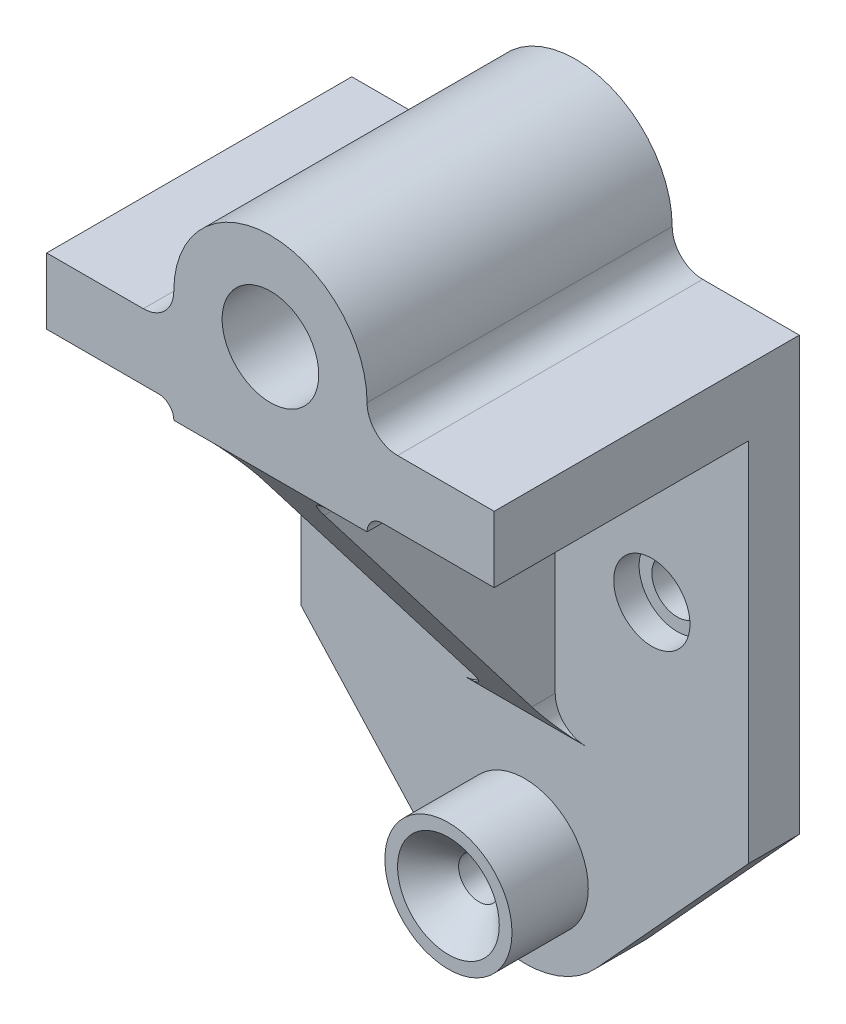
SolidWorks part; units mm, degrees
note: The reader was unsure of these and kept them because the rebuilt part matched: shared geometry of "Sketch5<11>", "Sketch2<10>", "Sketch5<9>".
ref_plane "Front Plane" through (0, 0, 0) normal (0, 0, 1) x (1, 0, 0)
ref_plane "Top Plane" through (0, 0, 0) normal (0, 1, 0) x (1, 0, 0)
ref_plane "Right Plane" through (0, 0, 0) normal (1, 0, 0) x (0, 0, -1)
sketch "Sketch2" plane through (0, 0, 0) normal (0, 0, 1) x (1, 0, 0)
  line L0 (44, 20) -> (14.0289, -12.8136)
  line L1 (44, 20) -> (44, 105)
  line L2 (44, 105) -> (25, 105)
  line L3 (0, 0) -> (0, 156.6134) construction
  line L4 (12, 89) -> (-12, 89)
  line L5 (44, 92) -> (22, 92)
  line L6 (-12, 24) -> (-9.5, 24)
  line L7 (19, 89) -> (12, 89)
  line L8 (6, 83) -> (6, 30)
  line L9 (12, 24) -> (9.5, 24)
  line L10 (9.5, 24) -> (-9.5, 24)
  line L11 (-6, 83) -> (-6, 30)
  line L12 (-19, 89) -> (-12, 89)
  line L13 (-44, 92) -> (-22, 92)
  line L14 (-44, 105) -> (-25, 105)
  line L15 (-44, 20) -> (-44, 105)
  line L16 (-44, 20) -> (-14.0289, -12.8136)
  arc A0 (-14.0289, -12.8136) -> (14.0289, -12.8136) centre (0, 0) ccw
  arc A1 (19, 111) -> (-19, 111) centre (0, 111) ccw
  arc A2 (25, 105) -> (19, 111) centre (25, 111) cw
  arc A3 (0, 101.5) -> (0, 120.5) centre (0, 111) ccw
  circle A4 centre (0, 0) radius 12.5
  circle A5 centre (0, 0) radius 4
  arc A6 (12, 24) -> (6, 30) centre (12, 30) cw
  arc A7 (12, 89) -> (6, 83) centre (12, 83) ccw
  arc A8 (22, 92) -> (19, 89) centre (22, 89) ccw
  circle A11 centre (0, 0) radius 10
  arc A14 (-22, 92) -> (-19, 89) centre (-22, 89) cw
  arc A15 (-12, 89) -> (-6, 83) centre (-12, 83) cw
  arc A16 (-12, 24) -> (-6, 30) centre (-12, 30) ccw
  arc A17 (0, 101.5) -> (0, 120.5) centre (0, 111) cw
  arc A18 (-25, 105) -> (-19, 111) centre (-25, 111) ccw
  point P30 (6, 24)
  point P40 (9.5, 111)
  point P52 (0, 24)
  point P53 (0, 89)
  dimension "D1" = 19
  dimension "D2" = 19
  dimension "D3" = 6
  dimension "D4" = 13
  dimension "D6" = 25
  dimension "D7" = 8
  dimension "D14" = 6
  dimension "D15" = 6
  dimension "D16" = 6
  dimension "D21" = 20
  dimension "D22" = 19
  dimension "D5" = 72
  dimension "D8" = 105
  dimension "D9" = 22
  dimension "D10" = 13
  dimension "D11" = 81
  dimension "D12" = 65
  dimension "D13" = 25
extrude "Boss-Extrude6" add sketch "Sketch2" along normal blind 60 contours A18 A1 A2 L2 L1 L0 A0 L16 L15 L14
sketch "Sketch5" plane through (0, 0, 60) normal (0, 0, 1) x (1, 0, 0)
  line L0 (44, 20) -> (44, 105) construction
  line L1 (-44, 20) -> (-44, 105) construction
  line L2 (12, 24) -> (9.5, 24) construction
  line L3 (-12, 24) -> (-9.5, 24) construction
  line L4 (9.5, 24) -> (-9.5, 24) construction
  line L5 (-44, 20) -> (-14.0289, -12.8136) construction
  line L6 (44, 20) -> (14.0289, -12.8136) construction
  line L7 (44, 92) -> (22, 92) construction
  line L8 (19, 89) -> (12, 89) construction
  line L9 (6, 83) -> (6, 30) construction
  line L10 (12, 89) -> (-12, 89) construction
  line L11 (-6, 83) -> (-6, 30) construction
  line L12 (-19, 89) -> (-12, 89) construction
  line L13 (-44, 92) -> (-22, 92) construction
  line L14 (44, 20) -> (44, 105)
  line L15 (-44, 20) -> (-44, 105)
  line L16 (12, 24) -> (9.5, 24)
  line L17 (-12, 24) -> (-9.5, 24)
  line L18 (9.5, 24) -> (-9.5, 24)
  line L19 (-44, 20) -> (-14.0289, -12.8136)
  line L20 (44, 20) -> (14.0289, -12.8136)
  line L21 (44, 92) -> (22, 92)
  line L22 (19, 89) -> (12, 89)
  line L23 (6, 83) -> (6, 30)
  line L24 (12, 89) -> (-12, 89)
  line L25 (-6, 83) -> (-6, 30)
  line L26 (-19, 89) -> (-12, 89)
  line L27 (-44, 92) -> (-22, 92)
  arc A0 (-6, 83) -> (-12, 89) centre (-12, 83) ccw construction
  arc A1 (-12, 24) -> (-6, 30) centre (-12, 30) ccw construction
  arc A2 (6, 30) -> (12, 24) centre (12, 30) ccw construction
  arc A3 (-14.0289, -12.8136) -> (14.0289, -12.8136) centre (0, 0) ccw construction
  circle A4 centre (0, 0) radius 4 construction
  circle A5 centre (0, 0) radius 10 construction
  circle A6 centre (0, 0) radius 12.5 construction
  arc A11 (22, 92) -> (19, 89) centre (22, 89) ccw construction
  arc A12 (12, 89) -> (6, 83) centre (12, 83) ccw construction
  arc A13 (-19, 89) -> (-22, 92) centre (-22, 89) ccw construction
  arc A14 (-12, 24) -> (-6, 30) centre (-12, 30) ccw
  arc A15 (6, 30) -> (12, 24) centre (12, 30) ccw
  arc A16 (-14.0289, -12.8136) -> (14.0289, -12.8136) centre (0, 0) ccw
  circle A17 centre (0, 0) radius 4
  circle A18 centre (0, 0) radius 10
  circle A19 centre (0, 0) radius 12.5
  arc A24 (22, 92) -> (19, 89) centre (22, 89) ccw
  arc A25 (12, 89) -> (6, 83) centre (12, 83) ccw
  arc A26 (-6, 83) -> (-12, 89) centre (-12, 83) ccw
  arc A27 (-19, 89) -> (-22, 92) centre (-22, 89) ccw
  circle A28 centre (0, 0) radius 4
  circle A29 centre (0, 0) radius 10
  circle A30 centre (0, 0) radius 12.5
extrude "Cut-Extrude3" cut sketch "Sketch5" against normal blind 50 and the other way through all
extrude "Boss-Extrude9" add sketch "Sketch5<11>" against normal blind 50 contours A26 L25 A14 L17 L18 L16 A15 L23 A25 L24
sketch "Sketch5<11>" plane through (0, 0, 60) normal (0, 0, 1) x (1, 0, 0) same geometry as "Sketch5"
sketch "Sketch25" plane through (6, 0, 0) normal (1, 0, 0) x (0, 0, -1)
  line L0 (-60, 89) -> (-10, 24)
  line L1 (-10, 24) -> (-60, 24) construction
  line L2 (-60, 30) -> (-60, 24) construction
  line L3 (-60, 83) -> (-60, 30) construction
  line L4 (-60, 89) -> (-60, 83) construction
  line L5 (-10, 24) -> (-60, 24)
  line L6 (-60, 30) -> (-60, 24)
  line L7 (-60, 83) -> (-60, 30)
  line L8 (-60, 89) -> (-60, 83)
extrude "Cut-Extrude7" cut sketch "Sketch25" against normal mid plane 50 contours L5 L6 L7 L8 L0
sketch "Sketch26" plane through (0, 0, 10) normal (0, 0, 1) x (1, 0, 0)
  line L0 (-44, 55) -> (44, 55) construction
  line L1 (-44, 20) -> (-44, 105) construction
  line L2 (44, 20) -> (44, 105) construction
  line L3 (-25, 105) -> (-25, -0.802) construction
  line L4 (-44, 20) -> (-14.0289, -12.8136) construction
  line L5 (25, 105) -> (25, -0.802) construction
  line L6 (44, 20) -> (14.0289, -12.8136) construction
  arc A0 (-25, 105) -> (-19, 111) centre (-25, 111) ccw construction
  point P12 (-25, 55)
  point P13 (25, 55)
  point P22 (25, 55)
  dimension "D1" = 50
hole_wizard "CBORE for M8 Hex Head Cap Screw3" positions "3DSketch9" profile "Sketch27" counterbore size "M8" standard "ANSI Metric"
sketch3d "3DSketch9"
  point P0 (-25, 55, 10)
  point P3 (25, 55, 10)
sketch "Sketch27" plane through (-25, 55, 10) normal (1, 0, 0) x (0, -1, 0)
  line L0 (0, 0) -> (0, 13.0043)
  line L1 (0, 13.0043) -> (5, 10)
  line L2 (5, 10) -> (5, 5)
  line L3 (5, 5) -> (7.5, 5)
  line L4 (7.5, 5) -> (7.5, 0)
  line L5 (7.5, 0) -> (0, 0)
  line L10 (0, 13.0043) -> (-5, 10) construction
  line L11 (0, -6.35) -> (0, 107.95) construction
  dimension "Hole Dia." = 10
  dimension "Hole Depth" = 10
  dimension "C'Bore Dia." = 15
  dimension "C'Bore Depth" = 5
  dimension "Drill Angle" = 118
sketch "Sketch28" plane through (0, 0, 60) normal (0, 0, 1) x (1, 0, 0)
  line L27 (-19, 89) -> (-12, 89)
  line L28 (-12, 89) -> (12, 89)
  line L29 (12, 89) -> (19, 89)
  line L30 (22, 92) -> (44, 92)
  line L31 (44, 92) -> (44, 105)
  line L32 (44, 105) -> (25, 105)
  line L33 (-25, 105) -> (-44, 105)
  line L34 (-44, 105) -> (-44, 92)
  line L35 (-44, 92) -> (-22, 92)
  line L36 (-19, 89) -> (-12, 89)
  line L37 (-12, 89) -> (12, 89)
  line L38 (12, 89) -> (19, 89)
  line L39 (22, 92) -> (44, 92)
  line L40 (44, 92) -> (44, 105)
  line L41 (44, 105) -> (25, 105)
  line L42 (-25, 105) -> (-44, 105)
  line L43 (-44, 105) -> (-44, 92)
  line L44 (-44, 92) -> (-22, 92)
  arc A10 (0, 101.5) -> (0, 120.5) centre (0, 111) ccw construction
  arc A11 (0, 120.5) -> (0, 101.5) centre (0, 111) ccw construction
  arc A12 (0, 101.5) -> (0, 120.5) centre (0, 111) ccw
  arc A13 (0, 120.5) -> (0, 101.5) centre (0, 111) ccw
  arc A15 (22, 92) -> (19, 89) centre (22, 89) ccw
  arc A16 (19, 111) -> (25, 105) centre (25, 111) ccw
  arc A17 (19, 111) -> (-19, 111) centre (0, 111) ccw
  arc A18 (-25, 105) -> (-19, 111) centre (-25, 111) ccw
  arc A19 (-19, 89) -> (-22, 92) centre (-22, 89) ccw
  arc A20 (22, 92) -> (19, 89) centre (22, 89) ccw
  arc A21 (19, 111) -> (25, 105) centre (25, 111) ccw
  arc A22 (19, 111) -> (-19, 111) centre (0, 111) ccw
  arc A23 (-25, 105) -> (-19, 111) centre (-25, 111) ccw
  arc A24 (-19, 89) -> (-22, 92) centre (-22, 89) ccw
  dimension "D1" = 0
extrude "Cut-Extrude8" cut sketch "Sketch28" against normal blind 60 contours A12 A13
sketch "Sketch29" plane through (0, 0, 10) normal (0, 0, 1) x (1, 0, 0)
  circle A0 centre (0, 0) radius 12.5 construction
  circle A1 centre (0, 0) radius 12.5
extrude "Boss-Extrude10" add sketch "Sketch29" along normal blind 15
extrude "Boss-Extrude11" add sketch "Sketch2<10>" against normal blind 15 contours A4
sketch "Sketch2<10>" plane through (0, 0, 0) normal (0, 0, 1) x (1, 0, 0) same geometry as "Sketch2"
sketch "Sketch32" plane through (0, 0, 25) normal (0, 0, 1) x (1, 0, 0)
  point P0 (0, 0)
extrude "Boss-Extrude8" add sketch "Sketch5<9>" against normal blind 50 contours A26 L25 A14 L17 L18 L16 A15 L23 A25 L24
sketch "Sketch5<9>" plane through (0, 0, 60) normal (0, 0, 1) x (1, 0, 0) same geometry as "Sketch5"
sketch "Sketch11" plane through (6, 0, 0) normal (1, 0, 0) x (0, 0, -1)
  line L0 (-10, 24) -> (-60, 89)
  line L3 (-60, 89) -> (-60, 83) construction
  line L4 (-10, 30) -> (-10, 24) construction
  line L5 (-60, 83) -> (-60, 30) construction
  line L6 (-60, 30) -> (-60, 24) construction
  line L7 (-10, 24) -> (-60, 24) construction
  line L8 (-60, 89) -> (-60, 83)
  line L9 (-10, 30) -> (-10, 24)
  line L10 (-60, 83) -> (-60, 30)
  line L11 (-60, 30) -> (-60, 24)
  line L12 (-10, 24) -> (-60, 24)
extrude "Cut-Extrude5" cut sketch "Sketch11" against normal mid plane 50 contours L9 L0 L4 L12 | L0 L8 L4 | L12 L0 L9 L11
hole_wizard "CSK for M8 Flat Head Machine Screw2" positions "3DSketch13" profile "Sketch34" countersink size "M8" standard "ANSI Metric"
sketch3d "3DSketch13"
  point P0 (0, 0, 0)
  point P3 (0, 0, 0)
  point P5 (0, 0, 25)
sketch "Sketch34" plane through (0, 0, 25) normal (1, 0, 0) x (0, -1, 0)
  line L0 (0, 0) -> (0, 42.4034)
  line L1 (0, 42.4034) -> (4, 40)
  line L2 (4, 40) -> (4, 6)
  line L3 (4, 6) -> (10, 0)
  line L5 (10, 0) -> (0, 0)
  line L6 (-4, 6) -> (-10, 0) construction
  line L10 (0, 42.4034) -> (-4, 40) construction
  line L11 (0, -6.35) -> (0, 107.95) construction
  dimension "Hole Dia." = 8
  dimension "Hole Depth" = 40
  dimension "Near C'Sink Dia." = 20
  dimension "Near C'Sink Angle" = 90
  dimension "Drill Angle" = 118
sketch "Sketch12" plane through (0, 0, 60) normal (0, 0, 1) x (1, 0, 0)
  line L9 (-12, 89) -> (12, 89)
  line L10 (12, 89) -> (19, 89)
  line L11 (22, 92) -> (44, 92)
  line L12 (44, 92) -> (44, 105)
  line L13 (44, 105) -> (25, 105)
  line L14 (-25, 105) -> (-44, 105)
  line L15 (-44, 105) -> (-44, 92)
  line L16 (-44, 92) -> (-22, 92)
  line L17 (-19, 89) -> (-12, 89)
  line L18 (-12, 89) -> (12, 89)
  line L19 (12, 89) -> (19, 89)
  line L20 (22, 92) -> (44, 92)
  line L21 (44, 92) -> (44, 105)
  line L22 (44, 105) -> (25, 105)
  line L23 (-25, 105) -> (-44, 105)
  line L24 (-44, 105) -> (-44, 92)
  line L25 (-44, 92) -> (-22, 92)
  line L26 (-19, 89) -> (-12, 89)
  arc A0 (0, 101.5) -> (0, 120.5) centre (0, 111) ccw construction
  arc A1 (0, 120.5) -> (0, 101.5) centre (0, 111) ccw construction
  arc A2 (0, 101.5) -> (0, 120.5) centre (0, 111) ccw
  arc A3 (0, 120.5) -> (0, 101.5) centre (0, 111) ccw
  arc A5 (22, 92) -> (19, 89) centre (22, 89) ccw
  arc A6 (19, 111) -> (25, 105) centre (25, 111) ccw
  arc A7 (19, 111) -> (-19, 111) centre (0, 111) ccw
  arc A8 (-25, 105) -> (-19, 111) centre (-25, 111) ccw
  arc A9 (-19, 89) -> (-22, 92) centre (-22, 89) ccw
  arc A10 (22, 92) -> (19, 89) centre (22, 89) ccw
  arc A11 (19, 111) -> (25, 105) centre (25, 111) ccw
  arc A12 (19, 111) -> (-19, 111) centre (0, 111) ccw
  arc A13 (-25, 105) -> (-19, 111) centre (-25, 111) ccw
  arc A14 (-19, 89) -> (-22, 92) centre (-22, 89) ccw
  dimension "D1" = 0
sketch "Sketch13" plane through (0, 0, 60) normal (0, 0, 1) x (1, 0, 0)
  line L9 (-12, 89) -> (12, 89)
  line L10 (12, 89) -> (19, 89)
  line L11 (22, 92) -> (44, 92)
  line L12 (44, 92) -> (44, 105)
  line L13 (44, 105) -> (25, 105)
  line L14 (-25, 105) -> (-44, 105)
  line L15 (-44, 105) -> (-44, 92)
  line L16 (-44, 92) -> (-22, 92)
  line L17 (-19, 89) -> (-12, 89)
  line L18 (-12, 89) -> (12, 89)
  line L19 (12, 89) -> (19, 89)
  line L20 (22, 92) -> (44, 92)
  line L21 (44, 92) -> (44, 105)
  line L22 (44, 105) -> (25, 105)
  line L23 (-25, 105) -> (-44, 105)
  line L24 (-44, 105) -> (-44, 92)
  line L25 (-44, 92) -> (-22, 92)
  line L26 (-19, 89) -> (-12, 89)
  arc A0 (0, 101.5) -> (0, 120.5) centre (0, 111) ccw construction
  arc A1 (0, 120.5) -> (0, 101.5) centre (0, 111) ccw construction
  arc A2 (0, 101.5) -> (0, 120.5) centre (0, 111) ccw
  arc A3 (0, 120.5) -> (0, 101.5) centre (0, 111) ccw
  arc A5 (22, 92) -> (19, 89) centre (22, 89) ccw
  arc A6 (19, 111) -> (25, 105) centre (25, 111) ccw
  arc A7 (19, 111) -> (-19, 111) centre (0, 111) ccw
  arc A8 (-25, 105) -> (-19, 111) centre (-25, 111) ccw
  arc A9 (-19, 89) -> (-22, 92) centre (-22, 89) ccw
  arc A10 (22, 92) -> (19, 89) centre (22, 89) ccw
  arc A11 (19, 111) -> (25, 105) centre (25, 111) ccw
  arc A12 (19, 111) -> (-19, 111) centre (0, 111) ccw
  arc A13 (-25, 105) -> (-19, 111) centre (-25, 111) ccw
  arc A14 (-19, 89) -> (-22, 92) centre (-22, 89) ccw
  dimension "D1" = 0
extrude "Cut-Extrude6" cut sketch "Sketch13" against normal blind 60 contours A2 A3
